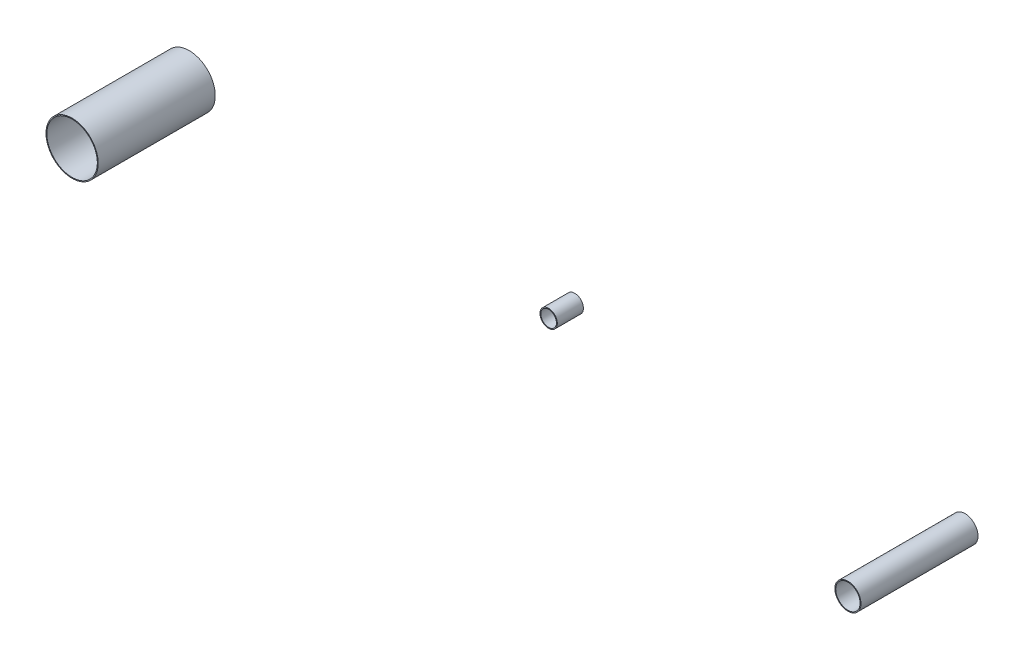
SolidWorks part; units mm, degrees
ref_plane "Plano frontal" through (0, 0, 0) normal (0, 0, 1) x (1, 0, 0)
ref_plane "Plano superior" through (0, 0, 0) normal (0, 1, 0) x (1, 0, 0)
ref_plane "Plano direito" through (0, 0, 0) normal (1, 0, 0) x (0, 0, -1)
sketch3d "3DSketch1"
  line L0 (-31937.4493, -16257.8595, 41013.2907) -> (-31937.4493, -16257.8595, 40727.0411) construction
  line L1 (-31937.4493, -16257.8595, 40995.9552) -> (-31937.4493, -16257.8595, 41013.2907) construction
  line L2 (-31937.4493, -16257.8595, 40727.0411) -> (-31494.4266, -16257.8595, 40727.0411) construction
  line L3 (-31494.4266, -16257.8595, 40727.0411) -> (-31494.4266, -16257.8595, 41013.2907) construction
  line L4 (-31494.4266, -16257.8595, 40727.0411) -> (-31046.0335, -16257.8595, 40727.0411) construction
  line L5 (-31046.0335, -16257.8595, 40727.0411) -> (-31046.0335, -16257.8595, 41013.2907) construction
  line L6 (-31937.4493, -16257.8595, 41013.2907) -> (-31937.4493, -16257.8595, 40878.7861)
  line L7 (-31494.4266, -16257.8595, 41013.2907) -> (-31494.4266, -16257.8595, 40878.7861)
  line L8 (-31046.0335, -16257.8595, 41013.2907) -> (-31046.0335, -16257.8595, 40878.7861)
  line L9 (-31937.4493, -16257.8595, 40878.7861) -> (-31937.4493, -16257.8595, 41013.2907)
sketch3d "3DSketch2"
  line L0 (-31937.4493, -16257.8595, 41013.2907) -> (-31937.4493, -16257.8595, 40878.7861)
sweep "Sweep-Thin2" add path "3DSketch2" circular profile diameter 60 parameters "D1"=1, "D3"=60
sketch3d "3DSketch3"
  line L0 (-31494.4266, -16257.8595, 40878.7861) -> (-31494.4266, -16257.8595, 40908.7861)
  point P4 (0, 0, 0)
sweep "Sweep-Thin3" add path "3DSketch3" circular profile diameter 20 parameters "D1"=1, "D3"=20
sketch3d "3DSketch4"
  line L0 (-31046.0335, -16257.8595, 41013.2907) -> (-31046.0335, -16257.8595, 40878.7861)
sweep "Sweep-Thin4" add path "3DSketch4" circular profile diameter 30 parameters "D1"=1, "D3"=30
